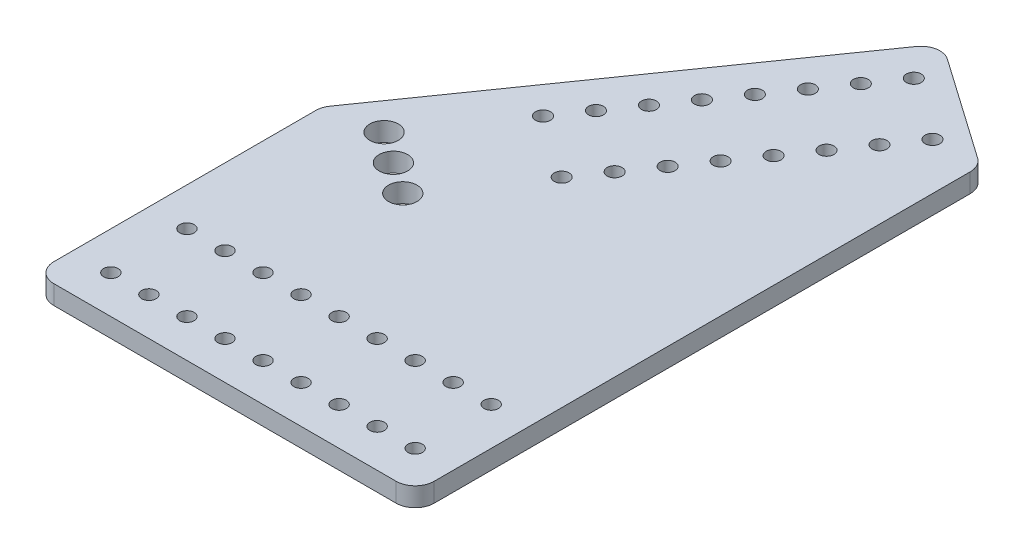
SolidWorks part; units mm, degrees
material "6061-T6 (SS)"
ref_plane "Front Plane" through (0, 0, 0) normal (0, 0, 1) x (1, 0, 0)
ref_plane "Top Plane" through (0, 0, 0) normal (0, 1, 0) x (1, 0, 0)
ref_plane "Right Plane" through (0, 0, 0) normal (1, 0, 0) x (0, 0, -1)
sketch "Sketch1" plane through (0, 0, 0) normal (0, 1, 0) x (1, 0, 0)
  line L0 (0, 95.8127) -> (85.3871, 217.7581)
  line L5 (0, 0) -> (127, 0)
  line L6 (0, 0) -> (0, 95.8127)
  line L7 (85.3871, 217.7581) -> (127, 217.7581) construction
  line L8 (127, 0) -> (127, 188.6204)
  line L9 (85.3871, 217.7581) -> (127, 188.6204)
  line L10 (127, 188.6204) -> (127, 217.7581) construction
  line L11 (0, 0) -> (-12.7, 0) construction
  line L12 (-12.7, 0) -> (-12.7, 77.6752) construction
  line L13 (0, 95.8127) -> (41.6129, 66.675) construction
  line L14 (0, 95.8127) -> (85.3871, 217.7581) construction
  line L15 (41.6129, 66.675) -> (127, 188.6204) construction
  line L16 (85.3871, 217.7581) -> (127, 188.6204) construction
  point P2 (70.2931, 199.8216)
  point P10 (0, 0)
  dimension "D1" = 66.675
  dimension "D2" = 127
  dimension "D3" = 55
  dimension "D4" = 50.8
  dimension "D5" = 12.7
  dimension "D6" = 12.7
extrude "Boss-Extrude1" add sketch "Sketch1" along normal blind 6.35
sketch "Sketch2" plane through (0, 6.35, 0) normal (0, 1, 0) x (1, 0, 0)
  line L0 (0, 0) -> (127, 0) construction
  line L1 (0, 95.8127) -> (0, 0) construction
  line L2 (90.5319, 202.9638) -> (111.3383, 188.395) construction
  line L3 (127, 188.6204) -> (85.3871, 217.7581) construction
  line L4 (85.3871, 217.7581) -> (0, 95.8127) construction
  line L5 (17.6877, 98.9315) -> (38.4941, 84.3627) construction
  line L6 (38.4941, 84.3627) -> (60.3474, 115.5723) construction
  line L7 (0, 95.8127) -> (41.6129, 66.675) construction
  line L8 (0, 95.8127) -> (85.3871, 217.7581) construction
  line L9 (41.6129, 66.675) -> (127, 188.6204) construction
  line L10 (85.3871, 217.7581) -> (127, 188.6204) construction
  circle A0 centre (12.7, 12.7) radius 2.413
  circle A2 centre (12.7, 38.1) radius 2.413
  circle A3 centre (25.4, 38.1) radius 2.413
  circle A4 centre (38.1, 38.1) radius 2.413
  circle A5 centre (50.8, 38.1) radius 2.413
  circle A6 centre (63.5, 38.1) radius 2.413
  circle A7 centre (25.4, 12.7) radius 2.413
  circle A8 centre (38.1, 12.7) radius 2.413
  circle A9 centre (50.8, 12.7) radius 2.413
  circle A10 centre (63.5, 12.7) radius 2.413
  circle A11 centre (76.2, 12.7) radius 2.413
  circle A12 centre (76.2, 38.1) radius 2.413
  circle A13 centre (88.9, 12.7) radius 2.413
  circle A14 centre (88.9, 38.1) radius 2.413
  circle A15 centre (101.6, 12.7) radius 2.413
  circle A16 centre (101.6, 38.1) radius 2.413
  circle A21 centre (90.5319, 202.9638) radius 2.4892
  circle A22 centre (111.3383, 188.395) radius 2.4892
  circle A23 centre (83.2474, 192.5606) radius 2.4892
  circle A24 centre (104.0539, 177.9917) radius 2.4892
  circle A25 centre (75.963, 182.1573) radius 2.4892
  circle A26 centre (96.7695, 167.5885) radius 2.4892
  circle A27 centre (68.6786, 171.7541) radius 2.4892
  circle A28 centre (89.4851, 157.1853) radius 2.4892
  circle A29 centre (61.3942, 161.3509) radius 2.4892
  circle A30 centre (82.2006, 146.782) radius 2.4892
  circle A31 centre (54.1098, 150.9476) radius 2.4892
  circle A32 centre (74.9162, 136.3788) radius 2.4892
  circle A33 centre (46.8253, 140.5444) radius 2.4892
  circle A34 centre (67.6318, 125.9756) radius 2.4892
  circle A35 centre (39.5409, 130.1412) radius 2.4892
  circle A36 centre (60.3474, 115.5723) radius 2.4892
  circle A37 centre (17.6877, 98.9315) radius 4.7625
  circle A38 centre (28.0909, 91.6471) radius 4.7625
  circle A39 centre (38.4941, 84.3627) radius 4.7625
  circle A40 centre (114.3, 12.7) radius 2.413
  circle A41 centre (114.3, 38.1) radius 2.413
  point P82 (85.3871, 217.7581)
  dimension "D1" = 4.826
  dimension "D2" = 12.7
  dimension "D3" = 12.7
  dimension "D6" = 25.4
  dimension "D7" = 12.7
  dimension "D8" = 50.8
  dimension "D9" = 4.9784
  dimension "D15" = 9.525
  dimension "D10" = 12.7
  dimension "D11" = 25.4
  dimension "D12" = 12.7
  dimension "D13" = 8
  dimension "D16" = 50.8
  dimension "D17" = 12.7
  dimension "D4" = 2
  dimension "D5" = 9
extrude "Cut-Extrude1" cut sketch "Sketch2" against normal through all
fillet "Fillet1" radius 6.35 5 edges at (85.3871, 3.175, -217.7581) (127, 3.175, -188.6204) (127, 3.175, 0) (0, 3.175, 0) (0, 3.175, -95.8127)
